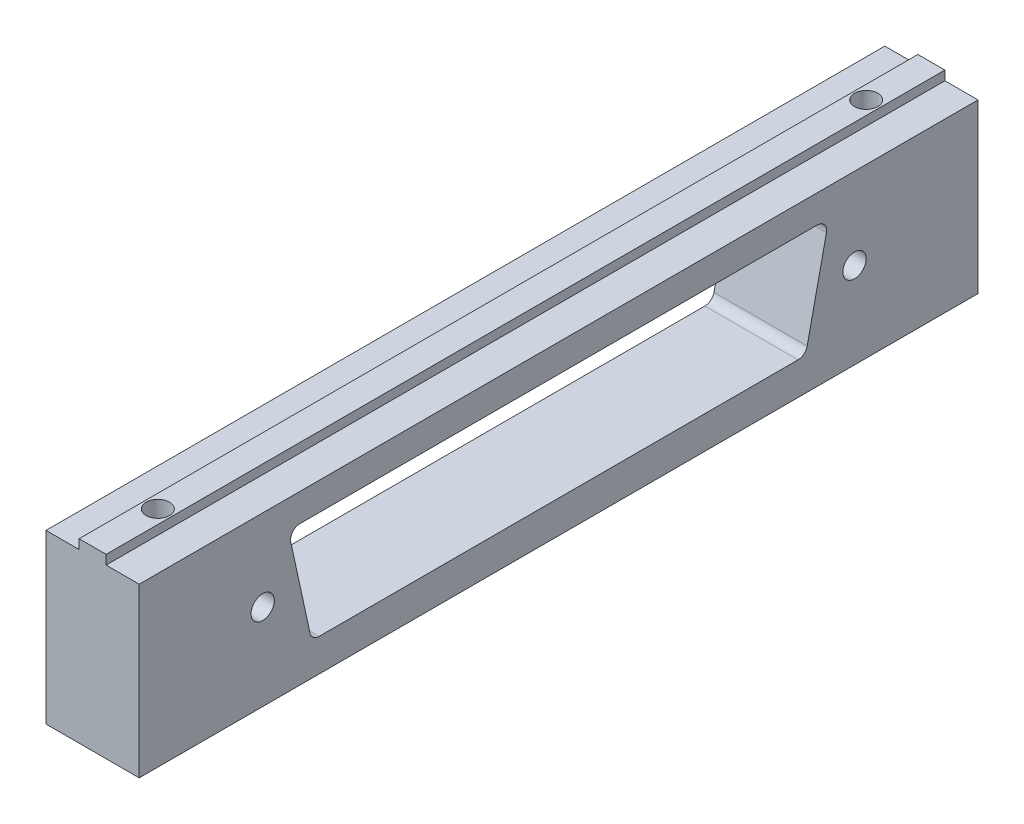
SolidWorks part; units mm, degrees
ref_plane "Front Plane" through (0, 0, 0) normal (0, 0, 1) x (1, 0, 0)
ref_plane "Top Plane" through (0, 0, 0) normal (0, 1, 0) x (1, 0, 0)
ref_plane "Right Plane" through (0, 0, 0) normal (1, 0, 0) x (0, 0, -1)
sketch "Sketch1" plane through (0, 0, 0) normal (0, 0, 1) x (1, 0, 0)
  line L0 (-5, 0) -> (5, 0)
  line L1 (5, 0) -> (5, 18)
  line L2 (5, 18) -> (1.45, 18)
  line L3 (1.45, 18) -> (1.45, 19)
  line L4 (1.45, 19) -> (-1.45, 19)
  line L5 (-1.45, 19) -> (-1.45, 18)
  line L6 (-1.45, 18) -> (-5, 18)
  line L7 (-5, 18) -> (-5, 0)
  point P9 (0, 0)
  dimension "D1" = 10
  dimension "D2" = 2.9
  dimension "D3" = 18
  dimension "D4" = 1
extrude "MakerBeamFix" add sketch "Sketch1" along normal mid plane 90
ref_plane "PlaneForMakerBeamHole" through (0, 11, 0) normal (0, 1, 0) x (1, 0, 0)
sketch "Sketch3" plane through (0, 0, 0) normal (0, -1, 0) x (1, 0, 0)
  circle A0 centre (0, 38) radius 4.25
  circle A1 centre (0, -38) radius 4.25
  point P4 (0, 0)
  point P7 (0, 0)
  dimension "D1" = 8.5
  dimension "D2" = 38
  dimension "D3" = 38
extrude "MakerBeamHoleForTool" cut sketch "Sketch3" against normal up to surface (11 mm away) up to plane "PlaneForMakerBeamHole"
sketch "Sketch5" plane through (0, 11, 0) normal (0, -1, 0) x (-1, 0, 0)
  circle A0 centre (0, 38) radius 1.25
  circle A1 centre (0, -38) radius 1.25
  circle A2 centre (0, -38) radius 4.25 construction
  circle A3 centre (0, 38) radius 4.25 construction
  dimension "D1" = 2.5
extrude "MakerBeamFixHole" cut sketch "Sketch5" against normal through all
sketch "Sketch4" plane through (-5, 0, 0) normal (-1, 0, 0) x (0, 0, 1)
  line L1 (-29, 15) -> (29, 15)
  line L2 (-29, 15) -> (-26.5, 3.5)
  line L3 (-26.5, 3.5) -> (26.5, 3.5)
  line L4 (29, 15) -> (26.5, 3.5)
  line L5 (45, 18) -> (-45, 18) construction
  circle A0 centre (-31.75, 9.25) radius 1.25
  circle A1 centre (31.75, 9.25) radius 1.25
  point P8 (-27.75, 9.25)
  point P9 (0, 0)
  point P11 (0, 3.5)
  point P13 (25.8742, 4.4846)
  point P14 (0, 0)
  dimension "D5" = 2.5
  dimension "D1" = 31.75
  dimension "D2" = 31.75
  dimension "D3" = 11.5
  dimension "D4" = 58
  dimension "D6" = 53
  dimension "D7" = 3
extrude "HoleForHartingConnector" cut sketch "Sketch4" against normal through all
fillet "Fillet1" radius 1 4 edges at (0, 15, -29) (0, 3.5, -26.5) (0, 3.5, 26.5) (0, 15, 29)
